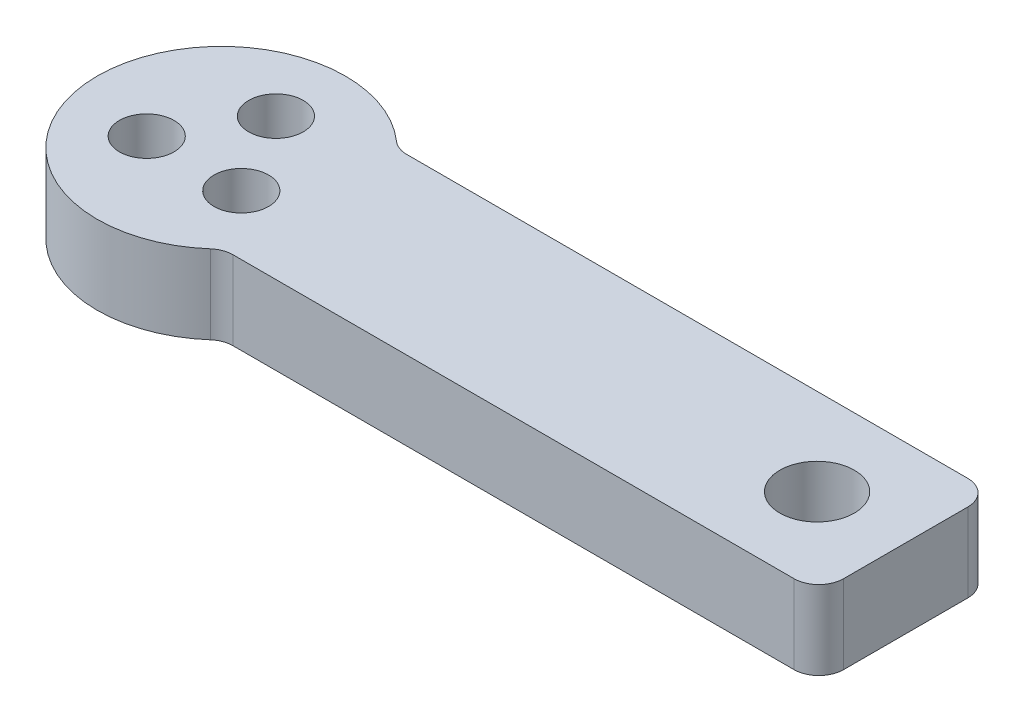
SolidWorks part; units mm, degrees
ref_plane "Front Plane" through (0, 0, 0) normal (0, 0, 1) x (1, 0, 0)
ref_plane "Top Plane" through (0, 0, 0) normal (0, 1, 0) x (1, 0, 0)
ref_plane "Right Plane" through (0, 0, 0) normal (1, 0, 0) x (0, 0, -1)
sketch "Sketch1" plane through (0, 0, 0) normal (0, 1, 0) x (1, 0, 0)
  line L0 (-5, 0) -> (27.5707, 0) construction
  line L1 (3.5707, 3.5) -> (27.5707, 3.5)
  line L3 (3.5707, -3.5) -> (27.5707, -3.5)
  line L4 (27.5707, 3.5) -> (27.5707, -3.5)
  arc A0 (3.5707, 3.5) -> (3.5707, -3.5) centre (0, 0) ccw
  circle A3 centre (24, 0) radius 1.5
  point P2 (0, 0)
  point P7 (27.5707, 0)
  dimension "D1" = 10
  dimension "D3" = 24
  dimension "D2" = 24
  dimension "D7" = 7
extrude "Boss-Extrude1" add sketch "Sketch1" along normal blind 3.175
sketch "Sketch2" plane through (0, 3.175, 0) normal (0, 1, 0) x (1, 0, 0)
  line L1 (1.9053, -1.1) -> (0, 2.2) construction
  line L2 (0, 2.2) -> (-1.9053, -1.1) construction
  line L3 (-1.9053, -1.1) -> (1.9053, -1.1) construction
  circle A0 centre (0, 0) radius 4 construction
  circle A1 centre (0, 0) radius 1.1 construction
  circle A2 centre (0, 2.2) radius 1.1
  circle A3 centre (1.9053, -1.1) radius 1.1
  circle A4 centre (-1.9053, -1.1) radius 1.1
  dimension "D1" = 8
  dimension "D2" = 2.2
  dimension "D3" = 2.2
fillet "Fillet1" radius 1 4 edges at (3.5707, 1.5875, -3.5) (3.5707, 1.5875, 3.5) (27.5707, 1.5875, -3.5) (27.5707, 1.5875, 3.5)
extrude "Cut-Extrude1" cut sketch "Sketch2" against normal up to surface (3.175 mm away) up to face at (14.362, 0, 0)
